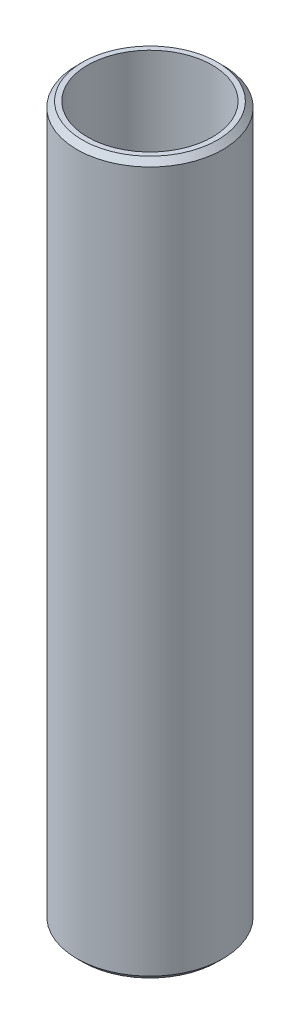
SolidWorks part; units mm, degrees
ref_plane "Front Plane" through (0, 0, 0) normal (0, 0, 1) x (1, 0, 0)
ref_plane "Top Plane" through (0, 0, 0) normal (0, 1, 0) x (1, 0, 0)
ref_plane "Right Plane" through (0, 0, 0) normal (1, 0, 0) x (0, 0, -1)
sketch "Sketch1" plane through (0, 0, 0) normal (0, 1, 0) x (1, 0, 0)
  circle A0 centre (0, 0) radius 60
  dimension "SHAFT_OD" = 120
extrude "Boss-Extrude1" add sketch "Sketch1" along normal blind 585.0431
sketch "Sketch2" plane through (0, 0, 0) normal (0, 1, 0) x (1, 0, 0)
  circle A0 centre (0, 0) radius 51.2705
  dimension "BORE_D" = 102.541
extrude "Cut-Extrude1" cut sketch "Sketch2" along normal through all
chamfer "Chamfer1" distance 4.5173 angle 45 2 edges at (0, 585.0431, 60) (0, 0, 60)
